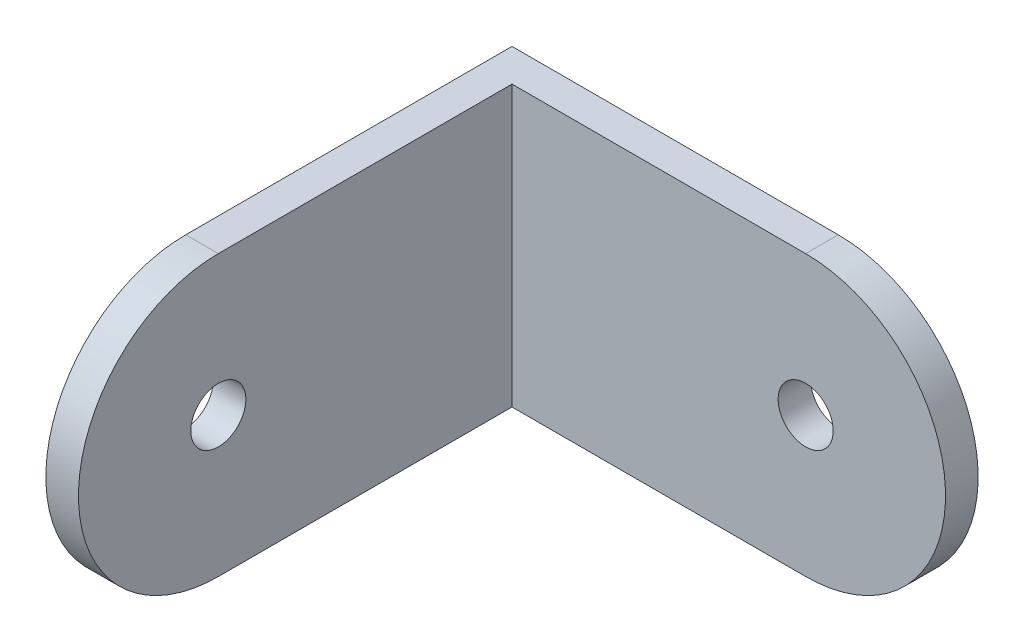
SolidWorks part; units mm, degrees
ref_plane "Front Plane" through (0, 0, 0) normal (0, 0, 1) x (1, 0, 0)
ref_plane "Top Plane" through (0, 0, 0) normal (0, 1, 0) x (1, 0, 0)
ref_plane "Right Plane" through (0, 0, 0) normal (1, 0, 0) x (0, 0, -1)
sketch "Sketch1" plane through (0, 0, 0) normal (0, 0, 1) x (1, 0, 0)
  line L0 (7.62, 0) -> (-17.78, 0) construction
  line L1 (-17.78, 7.62) -> (7.62, 7.62) construction
  line L2 (-17.78, 7.62) -> (-17.78, -7.62) construction
  line L3 (-17.78, -7.62) -> (7.62, -7.62) construction
  line L4 (7.62, 7.62) -> (7.62, -7.62) construction
  line L5 (-17.78, 7.62) -> (7.62, -7.62) construction
  line L6 (-17.78, -7.62) -> (7.62, 7.62) construction
  line L7 (0, 7.62) -> (-17.78, 7.62)
  line L8 (-17.78, 7.62) -> (-17.78, -7.62)
  line L9 (-17.78, -7.62) -> (0, -7.62)
  circle A0 centre (0, 0) radius 1.5
  circle A1 centre (0, 0) radius 7.62 construction
  arc A2 (0, 7.62) -> (0, -7.62) centre (0, 0) cw
  point P7 (-5.08, 0)
  dimension "D1" = 3
  dimension "D4" = 15.24
  dimension "D2" = 25.4
  dimension "D3" = 15.24
extrude "Boss-Extrude1" add sketch "Sketch1" along normal blind 1.778
sketch "Sketch2" plane through (-17.78, 0, 0) normal (-1, 0, 0) x (0, 0, 1)
  line L0 (1.778, -7.62) -> (0, -7.62) construction
  line L1 (0, 7.62) -> (17.78, 7.62)
  line L2 (0, 7.62) -> (0, -7.62)
  line L3 (0, -7.62) -> (17.78, -7.62)
  line L4 (17.78, 7.62) -> (17.78, -7.62) construction
  line L5 (0, 7.62) -> (17.78, -7.62) construction
  line L6 (0, -7.62) -> (17.78, 7.62) construction
  line L7 (25.4, 0) -> (0, 0) construction
  circle A0 centre (17.78, 0) radius 1.5
  circle A1 centre (17.78, 0) radius 7.62 construction
  arc A2 (17.78, 7.62) -> (17.78, -7.62) centre (17.78, 0) cw
  point P4 (8.89, 0)
  dimension "D1" = 3
  dimension "D2" = 25.4
extrude "Boss-Extrude2" add sketch "Sketch2" against normal blind 1.778
